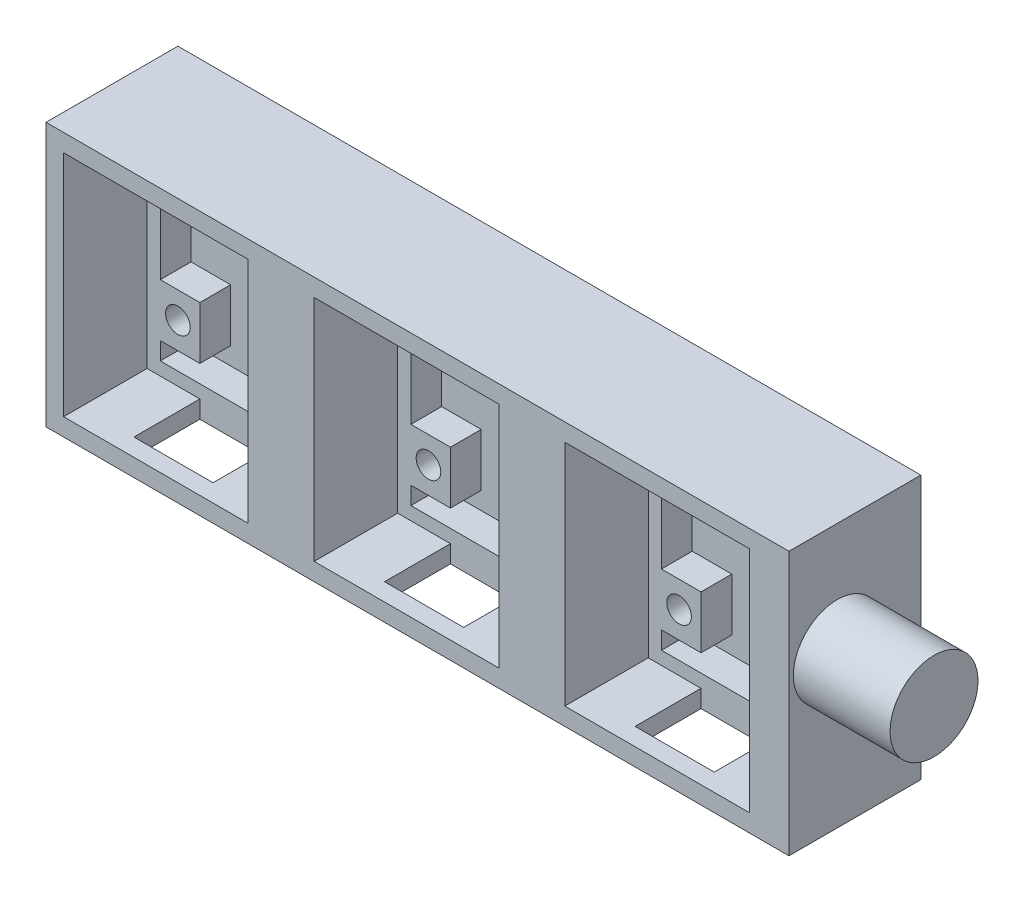
SolidWorks part; units mm, degrees
ref_plane "正面" through (0, 0, 0) normal (0, 0, 1) x (1, 0, 0)
ref_plane "平面" through (0, 0, 0) normal (0, 1, 0) x (1, 0, 0)
ref_plane "右側面" through (0, 0, 0) normal (1, 0, 0) x (0, 0, -1)
sketch "ｽｹｯﾁ1" plane through (0, 0, 0) normal (0, 0, 1) x (1, 0, 0)
  line L1 (-83.9031, 40.6786) -> (0.5969, 40.6786)
  line L2 (-83.9031, 40.6786) -> (-83.9031, 10.6786)
  line L3 (-83.9031, 10.6786) -> (0.5969, 10.6786)
  line L4 (0.5969, 40.6786) -> (0.5969, 10.6786)
  dimension "D1" = 30
  dimension "D2" = 84.5
extrude "ﾎﾞｽ - 押し出し1" add sketch "ｽｹｯﾁ1" along normal blind 15
sketch "ｽｹｯﾁ2" plane through (0, 0, 15) normal (0, 0, 1) x (1, 0, 0)
  line L0 (0.5969, 40.6786) -> (-83.9031, 40.6786) construction
  line L1 (-81.9031, 38.6786) -> (-60.9031, 38.6786)
  line L2 (-81.9031, 38.6786) -> (-81.9031, 12.6786)
  line L3 (-81.9031, 12.6786) -> (-60.9031, 12.6786)
  line L4 (-60.9031, 38.6786) -> (-60.9031, 12.6786)
  line L5 (-83.9031, 10.6786) -> (0.5969, 10.6786) construction
  line L7 (-83.9031, 40.6786) -> (-83.9031, 10.6786) construction
  line L8 (-58.9031, 40.6786) -> (-58.9031, 10.6786) construction
  line L9 (-55.4031, 40.6786) -> (-55.4031, 10.6786) construction
  line L10 (-30.4031, 40.6786) -> (-30.4031, 10.6786) construction
  line L11 (-26.9031, 40.6786) -> (-26.9031, 10.6786) construction
  line L12 (-1.9031, 40.6786) -> (-1.9031, 10.6786) construction
  line L13 (1.5969, 40.6786) -> (1.5969, 10.6786) construction
  line L18 (-53.4031, 38.6786) -> (-32.4031, 38.6786)
  line L19 (-53.4031, 38.6786) -> (-53.4031, 12.6786)
  line L20 (-53.4031, 12.6786) -> (-32.4031, 12.6786)
  line L21 (-32.4031, 38.6786) -> (-32.4031, 12.6786)
  line L22 (-24.9031, 38.6786) -> (-3.9031, 38.6786)
  line L23 (-24.9031, 38.6786) -> (-24.9031, 12.6786)
  line L24 (-24.9031, 12.6786) -> (-3.9031, 12.6786)
  line L25 (-3.9031, 38.6786) -> (-3.9031, 12.6786)
  dimension "D1" = 26
  dimension "D2" = 21
  dimension "D3" = 2
  dimension "D4" = 2
  dimension "D5" = 2
  dimension "D6" = 2
  dimension "D7" = 25
  dimension "D8" = 3.5
  dimension "D9" = 25
  dimension "D10" = 3.5
  dimension "D11" = 25
  dimension "D12" = 3.5
  dimension "D15" = 2
  dimension "D16" = 21
  dimension "D17" = 2
  dimension "D18" = 21
  dimension "D19" = 2
  dimension "D21" = 2
extrude "ｶｯﾄ - 押し出し1" cut sketch "ｽｹｯﾁ2" against normal blind 13
sketch "ｽｹｯﾁ3" plane through (0, 0, 2) normal (0, 0, 1) x (1, 0, 0)
  line L0 (-53.4031, 38.6786) -> (-53.4031, 12.6786) construction
  line L1 (-60.9031, 38.6786) -> (-81.9031, 38.6786)
  line L2 (-60.9031, 38.6786) -> (-60.9031, 12.6786)
  line L3 (-60.9031, 12.6786) -> (-81.9031, 12.6786)
  line L4 (-81.9031, 38.6786) -> (-81.9031, 12.6786)
  line L5 (-80.4031, 37.1786) -> (-62.4031, 37.1786)
  line L6 (-80.4031, 37.1786) -> (-80.4031, 14.1786)
  line L7 (-80.4031, 14.1786) -> (-62.4031, 14.1786)
  line L8 (-62.4031, 37.1786) -> (-62.4031, 14.1786)
  line L9 (-51.9031, 37.1786) -> (-33.9031, 37.1786)
  line L10 (-51.9031, 37.1786) -> (-51.9031, 14.1786)
  line L11 (-51.9031, 14.1786) -> (-33.9031, 14.1786)
  line L12 (-33.9031, 37.1786) -> (-33.9031, 14.1786)
  line L13 (-23.4031, 37.1786) -> (-5.4031, 37.1786)
  line L14 (-23.4031, 37.1786) -> (-23.4031, 14.1786)
  line L15 (-23.4031, 14.1786) -> (-5.4031, 14.1786)
  line L16 (-5.4031, 37.1786) -> (-5.4031, 14.1786)
  line L21 (-24.9031, 38.6786) -> (-24.9031, 12.6786) construction
  line L24 (-53.4031, 38.6786) -> (-32.4031, 38.6786)
  line L25 (-53.4031, 38.6786) -> (-53.4031, 12.6786)
  line L26 (-53.4031, 12.6786) -> (-32.4031, 12.6786)
  line L27 (-32.4031, 38.6786) -> (-32.4031, 12.6786)
  line L28 (-24.9031, 38.6786) -> (-3.9031, 38.6786)
  line L29 (-24.9031, 38.6786) -> (-24.9031, 12.6786)
  line L30 (-24.9031, 12.6786) -> (-3.9031, 12.6786)
  line L31 (-3.9031, 38.6786) -> (-3.9031, 12.6786)
  dimension "D1" = 1.5
  dimension "D2" = 1.5
  dimension "D3" = 1.5
  dimension "D4" = 1.5
  dimension "D5" = 1.5
  dimension "D6" = 1.5
  dimension "D8" = 26
  dimension "D9" = 21
  dimension "D10" = 26
  dimension "D11" = 21
extrude "ﾎﾞｽ - 押し出し2" add sketch "ｽｹｯﾁ3" along normal blind 3.5
sketch "ｽｹｯﾁ5" plane through (0, 0, 2) normal (0, 0, 1) x (1, 0, 0)
  line L0 (-62.4031, 14.1786) -> (-62.4031, 37.1786) construction
  line L1 (-62.4031, 22.1786) -> (-66.9031, 22.1786)
  line L2 (-62.4031, 22.1786) -> (-62.4031, 16.1786)
  line L3 (-62.4031, 16.1786) -> (-66.9031, 16.1786)
  line L4 (-66.9031, 22.1786) -> (-66.9031, 16.1786)
  line L5 (-51.9031, 37.1786) -> (-51.9031, 14.1786) construction
  line L6 (-81.9031, 12.6786) -> (-60.9031, 12.6786) construction
  line L7 (-80.4031, 37.1786) -> (-80.4031, 14.1786) construction
  line L8 (-80.4031, 22.1786) -> (-75.9031, 22.1786)
  line L9 (-80.4031, 22.1786) -> (-80.4031, 16.1786)
  line L10 (-80.4031, 16.1786) -> (-75.9031, 16.1786)
  line L11 (-75.9031, 22.1786) -> (-75.9031, 16.1786)
  line L12 (-51.9031, 22.1786) -> (-47.4031, 22.1786)
  line L13 (-51.9031, 22.1786) -> (-51.9031, 16.1786)
  line L14 (-51.9031, 16.1786) -> (-47.4031, 16.1786)
  line L15 (-47.4031, 22.1786) -> (-47.4031, 16.1786)
  line L16 (-33.9031, 14.1786) -> (-33.9031, 37.1786) construction
  line L17 (-33.9031, 22.1786) -> (-38.4031, 22.1786)
  line L18 (-33.9031, 22.1786) -> (-33.9031, 16.1786)
  line L19 (-33.9031, 16.1786) -> (-38.4031, 16.1786)
  line L20 (-38.4031, 22.1786) -> (-38.4031, 16.1786)
  line L21 (-23.4031, 37.1786) -> (-23.4031, 14.1786) construction
  line L22 (-23.4031, 22.1786) -> (-18.9031, 22.1786)
  line L23 (-23.4031, 22.1786) -> (-23.4031, 16.1786)
  line L24 (-23.4031, 16.1786) -> (-18.9031, 16.1786)
  line L25 (-18.9031, 22.1786) -> (-18.9031, 16.1786)
  line L26 (-5.4031, 14.1786) -> (-5.4031, 37.1786) construction
  line L27 (-5.4031, 22.1786) -> (-9.9031, 22.1786)
  line L28 (-5.4031, 22.1786) -> (-5.4031, 16.1786)
  line L29 (-5.4031, 16.1786) -> (-9.9031, 16.1786)
  line L30 (-9.9031, 22.1786) -> (-9.9031, 16.1786)
  point P10 (-66.9031, 19.1786)
  point P15 (-75.9031, 19.1786)
  dimension "D1" = 4.5
  dimension "D2" = 6
  dimension "D3" = 6.5
  dimension "D4" = 6.5
extrude "ﾎﾞｽ - 押し出し3" add sketch "ｽｹｯﾁ5" along normal blind 3.5
sketch "ｽｹｯﾁ6" plane through (0, 0, 5.5) normal (0, 0, 1) x (1, 0, 0)
  line L0 (-66.9031, 22.1786) -> (-66.9031, 16.1786) construction
  line L1 (-66.9031, 16.1786) -> (-62.4031, 16.1786) construction
  line L2 (-75.9031, 16.1786) -> (-75.9031, 22.1786) construction
  line L3 (-80.4031, 16.1786) -> (-75.9031, 16.1786) construction
  line L4 (-47.4031, 16.1786) -> (-47.4031, 22.1786) construction
  line L5 (-51.9031, 16.1786) -> (-47.4031, 16.1786) construction
  line L6 (-38.4031, 22.1786) -> (-38.4031, 16.1786) construction
  line L7 (-38.4031, 16.1786) -> (-33.9031, 16.1786) construction
  line L8 (-18.9031, 16.1786) -> (-18.9031, 22.1786) construction
  line L9 (-23.4031, 16.1786) -> (-18.9031, 16.1786) construction
  line L10 (-9.9031, 22.1786) -> (-9.9031, 16.1786) construction
  line L11 (-9.9031, 16.1786) -> (-5.4031, 16.1786) construction
  circle A0 centre (-64.4031, 19.1786) radius 1.4
  circle A1 centre (-78.4031, 19.1786) radius 1.4
  circle A2 centre (-49.9031, 19.1786) radius 1.4
  circle A3 centre (-35.9031, 19.1786) radius 1.4
  circle A4 centre (-21.4031, 19.1786) radius 1.4
  circle A5 centre (-7.4031, 19.1786) radius 1.4
  dimension "D1" = 2.8
  dimension "D4" = 2.5
  dimension "D5" = 3
  dimension "D6" = 2.5
  dimension "D2" = 2.5
  dimension "D3" = 3
  dimension "D7" = 3
  dimension "D8" = 2.5
  dimension "D9" = 3
  dimension "D10" = 2.5
  dimension "D11" = 3
  dimension "D12" = 2.5
  dimension "D13" = 3
extrude "ｶｯﾄ - 押し出し2" cut sketch "ｽｹｯﾁ6" against normal through all
sketch "ｽｹｯﾁ7" plane through (0, 12.6786, 0) normal (0, 1, 0) x (1, 0, 0)
  line L0 (-81.9031, -5.5) -> (-60.9031, -5.5) construction
  line L1 (-66.9031, -5.5) -> (-75.9031, -5.5)
  line L2 (-66.9031, -5.5) -> (-66.9031, -13)
  line L3 (-66.9031, -13) -> (-75.9031, -13)
  line L4 (-75.9031, -5.5) -> (-75.9031, -13)
  line L5 (-81.9031, -15) -> (-60.9031, -15) construction
  line L6 (-60.9031, -5.5) -> (-60.9031, -15) construction
  line L7 (-81.9031, -5.5) -> (-81.9031, -15) construction
  line L8 (-53.4031, -5.5) -> (-32.4031, -5.5) construction
  line L9 (-38.4031, -5.5) -> (-47.4031, -5.5)
  line L10 (-38.4031, -5.5) -> (-38.4031, -13)
  line L11 (-38.4031, -13) -> (-47.4031, -13)
  line L12 (-47.4031, -5.5) -> (-47.4031, -13)
  line L13 (-24.9031, -5.5) -> (-3.9031, -5.5) construction
  line L14 (-9.9031, -5.5) -> (-18.9031, -5.5)
  line L15 (-9.9031, -5.5) -> (-9.9031, -13)
  line L16 (-9.9031, -13) -> (-18.9031, -13)
  line L17 (-18.9031, -5.5) -> (-18.9031, -13)
  line L23 (-53.4031, -5.5) -> (-53.4031, -15) construction
  line L24 (-24.9031, -5.5) -> (-24.9031, -15) construction
  dimension "D1" = 2
  dimension "D2" = 6
  dimension "D3" = 6
  dimension "D4" = 7.5
  dimension "D5" = 9
  dimension "D6" = 7.5
  dimension "D7" = 9
  dimension "D10" = 6
  dimension "D11" = 6
extrude "ｶｯﾄ - 押し出し3" cut sketch "ｽｹｯﾁ7" against normal through all
sketch "ｽｹｯﾁ13" plane through (-83.9031, 0, 0) normal (-1, 0, 0) x (0, 0, 1)
  line L0 (0, 40.6786) -> (0, 10.6786) construction
  line L1 (0, 35.5786) -> (1.8, 35.5786)
  line L2 (0, 35.5786) -> (0, 30.7786)
  line L3 (0, 30.7786) -> (1.8, 30.7786)
  line L4 (1.8, 35.5786) -> (1.8, 30.7786)
  line L5 (15, 10.6786) -> (0, 10.6786) construction
  line L6 (0, 20.5786) -> (1.8, 20.5786)
  line L7 (0, 20.5786) -> (0, 15.7786)
  line L8 (0, 15.7786) -> (1.8, 15.7786)
  line L9 (1.8, 20.5786) -> (1.8, 15.7786)
  line L10 (15, 40.6786) -> (0, 40.6786) construction
  dimension "D1" = 4.8
  dimension "D2" = 4.8
  dimension "D3" = 1.8
  dimension "D5" = 5.1
  dimension "D6" = 5.1
extrude "ﾎﾞｽ - 押し出し4" add sketch "ｽｹｯﾁ13" along normal blind 3
sketch "ｽｹｯﾁ14" plane through (0.5969, 0, 0) normal (1, 0, 0) x (0, 0, -1)
  line L0 (-15, 10.6786) -> (-15, 40.6786) construction
  line L1 (-15, 10.6786) -> (0, 10.6786) construction
  circle A0 centre (-9.5, 28.1786) radius 5
  dimension "D1" = 10
  dimension "D2" = 5.5
  dimension "D3" = 17.5
extrude "ﾎﾞｽ - 押し出し5" add sketch "ｽｹｯﾁ14" along normal blind 11
sketch "ｽｹｯﾁ15" plane through (0, 0, 0) normal (0, 0, -1) x (-1, 0, 0)
  line L0 (-0.5969, 40.6786) -> (83.9031, 40.6786) construction
  line L1 (9.4031, 25.6786) -> (9.4031, 40.6786) construction
  line L2 (9.4031, 25.6786) -> (9.4031, 10.6786) construction
  line L3 (83.9031, 10.6786) -> (-0.5969, 10.6786) construction
  line L4 (-0.5969, 10.6786) -> (-0.5969, 40.6786) construction
  line L6 (5.4031, 29.6786) -> (13.4031, 29.6786)
  line L7 (5.4031, 29.6786) -> (5.4031, 21.6786)
  line L8 (5.4031, 21.6786) -> (13.4031, 21.6786)
  line L9 (13.4031, 29.6786) -> (13.4031, 21.6786)
  line L10 (5.4031, 29.6786) -> (13.4031, 21.6786) construction
  line L11 (5.4031, 21.6786) -> (13.4031, 29.6786) construction
  dimension "D1" = 10
  dimension "D2" = 8
  dimension "D3" = 8
extrude "ｶｯﾄ - 押し出し4" cut sketch "ｽｹｯﾁ15" against normal blind 10
